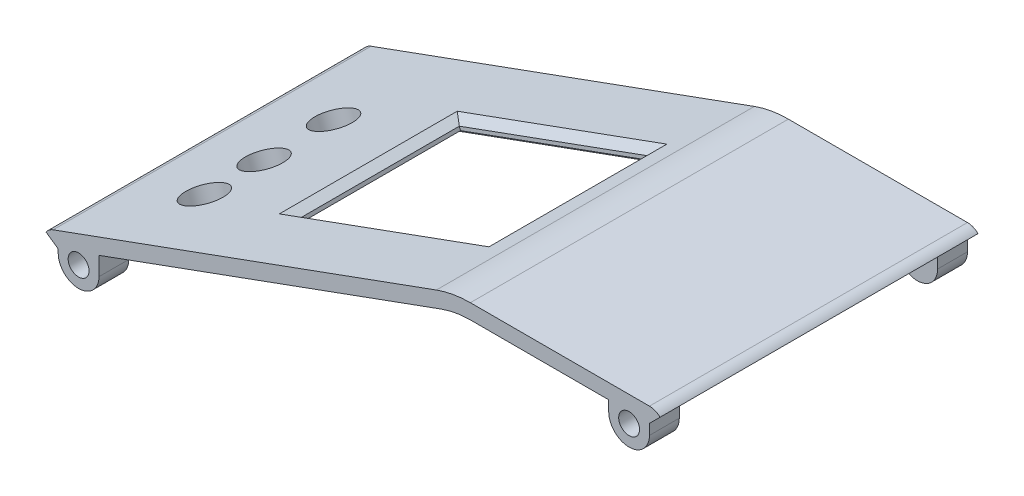
SolidWorks part; units mm, degrees
ref_plane "Спереди" through (0, 0, 0) normal (0, 0, 1) x (1, 0, 0)
ref_plane "Сверху" through (0, 0, 0) normal (0, 1, 0) x (1, 0, 0)
ref_plane "Справа" through (0, 0, 0) normal (1, 0, 0) x (0, 0, -1)
sketch "Эскиз1" plane through (0, 0, 0) normal (0, 0, 1) x (1, 0, 0)
  line L0 (-59.5, 47.8994) -> (-61.9575, 49.6201) construction
  line L1 (59.5, 80) -> (23.4509, 80)
  line L5 (-59.5, 47.8994) -> (17.6365, 75.9748)
  line L6 (23.4509, 77) -> (59.5, 77)
  line L8 (-59.5, 47.8994) -> (-61.9575, 49.6201)
  line L10 (61.6213, 79.1213) -> (59.5, 77) construction
  line L11 (61.6213, 79.1213) -> (59.5, 77)
  line L12 (-60.5261, 50.7185) -> (16.6105, 78.7939)
  arc A0 (23.4509, 80) -> (16.6105, 78.7939) centre (23.4509, 60) ccw
  arc A1 (17.6365, 75.9748) -> (23.4509, 77) centre (23.4509, 60) cw
  arc A2 (61.6213, 79.1213) -> (59.5, 80) centre (59.5, 77) ccw construction
  arc A3 (61.6213, 79.1213) -> (59.5, 80) centre (59.5, 77) ccw
  arc A5 (-60.5261, 50.7185) -> (-61.9575, 49.6201) centre (-59.5, 47.8994) ccw construction
  arc A6 (-60.5261, 50.7185) -> (-61.9575, 49.6201) centre (-59.5, 47.8994) ccw
  dimension "D3" = 20
  dimension "D4" = 17
  dimension "D2" = 20
extrude "Бобышка-Вытянуть1" add sketch "Эскиз1" along normal mid plane 64
sketch "Эскиз2" plane through (0, 0, 0) normal (0, 0, 1) x (1, 0, 0)
  line L1 (16.6105, 78.7939) -> (-60.5261, 50.7185) construction
  line L2 (51.3, 80) -> (51.3, 74.9)
  line L5 (59.5, 74.9) -> (59.5, 80)
  line L6 (59.5, 80) -> (23.4509, 80) construction
  line L7 (59.5, 80) -> (51.3, 80)
  line L9 (-51.3, 54.0765) -> (-51.3, 47.1569)
  line L11 (-59.5, 3) -> (-59.5, 47.8994) construction
  line L12 (-59.5, 47.1569) -> (-59.5, 51.0919)
  line L13 (-59.5, 51.0919) -> (-51.3, 54.0765)
  arc A0 (51.3, 74.9) -> (59.5, 74.9) centre (55.4, 74.9) ccw
  circle A1 centre (55.4, 74.9) radius 2.1
  arc A2 (-51.3, 47.1569) -> (-59.5, 47.1569) centre (-55.4, 47.1569) cw
  circle A3 centre (-55.4, 47.1569) radius 2.1
  dimension "D1" = 4.2
  dimension "D2" = 2
  dimension "D3" = 3
  dimension "D4" = 2
  dimension "D5" = 3
extrude "Бобышка-Вытянуть2" add sketch "Эскиз2" against normal blind 6 from surface contours L2 A0 L5 L7 A1 | A1 | A2 L9 L13 L12 A3 | A3 region at (55.4, 79.8768, 0) region at (-51.4374, 50.6167, 0) region at (55.4, 74.9, 0) region at (-55.4, 47.1569, 0) starting at face at (7.9692, 69.7003, 32)
extrude "Бобышка-Вытянуть3" add sketch "Эскиз2<3>" along normal blind 6 from surface contours A1 | L2 A0 L5 L7 A1 | A2 L9 L13 L12 A3 | A3 region at (55.4, 79.8768, 0) region at (-51.4374, 50.6167, 0) region at (55.4, 74.9, 0) region at (-55.4, 47.1569, 0) starting at face at (7.9692, 69.7003, -32)
sketch "Эскиз2<3>" plane through (0, 0, 0) normal (0, 0, 1) x (1, 0, 0) same geometry as "Эскиз2"
extrude "Вырез-Вытянуть1" cut sketch "Эскиз2<4>" against normal blind 4 from surface contours A1 | A3 region at (55.4, 74.9, 0) region at (-55.4, 47.1569, 0) starting at face at (4.9807, 66.3, 32)
sketch "Эскиз2<4>" plane through (0, 0, 0) normal (0, 0, 1) x (1, 0, 0) same geometry as "Эскиз2"
extrude "Вырез-Вытянуть2" cut sketch "Эскиз2<5>" along normal blind 4 from surface contours A1 | A3 region at (55.4, 74.9, 0) region at (-55.4, 47.1569, 0) starting at face at (4.9807, 66.3, -32)
sketch "Эскиз2<5>" plane through (0, 0, 0) normal (0, 0, 1) x (1, 0, 0) same geometry as "Эскиз2"
sketch "Эскиз3" plane through (-22.3547, 61.4191, 0) normal (0.342, -0.9397, 0) x (0.9397, 0.342, 0)
  line L8 (-9.7792, -17.5) -> (-9.7792, -14.8)
  line L9 (38.4208, -17.5) -> (-9.7792, -17.5)
  line L10 (38.4208, 17.5) -> (38.4208, -17.5)
  line L11 (-9.5792, 17.5) -> (38.4208, 17.5)
  line L12 (-9.7792, -17.5) -> (-9.7792, 17.5)
  line L13 (38.4208, -17.5) -> (-9.7792, -17.5)
  line L14 (38.4208, 17.5) -> (38.4208, -17.5)
  line L15 (-9.7792, 17.5) -> (38.4208, 17.5)
  dimension "D1" = 0.2
extrude "Вырез-Вытянуть3" cut sketch "Эскиз3" against normal blind 0.8
sketch "Эскиз4" plane through (-22.3547, 61.4191, 0) normal (0.342, -0.9397, 0) x (0.9397, 0.342, 0)
  line L16 (-4.5792, -16.4) -> (37.3208, -16.4)
  line L17 (-4.5792, 16.4) -> (-4.5792, -16.4)
  line L18 (37.3208, 16.4) -> (-4.5792, 16.4)
  line L19 (37.3208, -16.4) -> (37.3208, 16.4)
  line L20 (-4.5792, -16.4) -> (37.3208, -16.4)
  line L21 (-4.5792, 16.4) -> (-4.5792, -16.4)
  line L22 (37.3208, 16.4) -> (-4.5792, 16.4)
  line L23 (37.3208, -16.4) -> (37.3208, 16.4)
  dimension "D1" = 0.5
extrude "Вырез-Вытянуть4" cut sketch "Эскиз4" against normal through all
sketch "Эскиз7" plane through (-23.3808, 64.2382, 0) normal (-0.342, 0.9397, 0) x (0.9397, 0.342, 0)
  circle A2 centre (-24.4292, 10.25) radius 4
  circle A3 centre (-24.4292, 10.25) radius 4
  circle A20 centre (-24.4142, -3.75) radius 4
  circle A21 centre (-24.4142, -15.75) radius 4
  dimension "D2" = 8
  dimension "D1" = 0.5
extrude "Вырез-Вытянуть5" cut sketch "Эскиз7" against normal blind 10
sketch "Эскиз8" plane through (-22.3547, 61.4191, 0) normal (0.342, -0.9397, 0) x (0.9397, 0.342, 0)
  line L0 (38.4208, -17.5) -> (38.4208, 17.5) construction
  circle A1 centre (40.9708, 15) radius 2.55
  circle A4 centre (40.9708, -15) radius 2.55
  circle A7 centre (-36.0292, -16.5) radius 2.55
  circle A8 centre (-36.0292, 16.5) radius 2.55
extrude "Бобышка-Вытянуть4" add sketch "Эскиз8" along normal up to surface (2 mm away)
sketch "Эскиз9" plane through (-21.6707, 59.5398, 0) normal (0.342, -0.9397, 0) x (0.9397, 0.342, 0)
  circle A0 centre (40.9708, -15) radius 1.4
  circle A1 centre (40.9708, 15) radius 1.4
  circle A2 centre (-36.0292, -16.5) radius 1.4
  circle A3 centre (-36.0292, 16.5) radius 1.4
  dimension "D1" = 2.8
extrude "Вырез-Вытянуть6" cut sketch "Эскиз9" against normal blind 3
chamfer "Фаска1" distance 1.5 angle 45 4 edges at (-27.6838, 62.6721, 0) (-7.9972, 69.8374, -16.4) (11.6893, 77.0027, 0) (-7.9972, 69.8374, 16.4)
